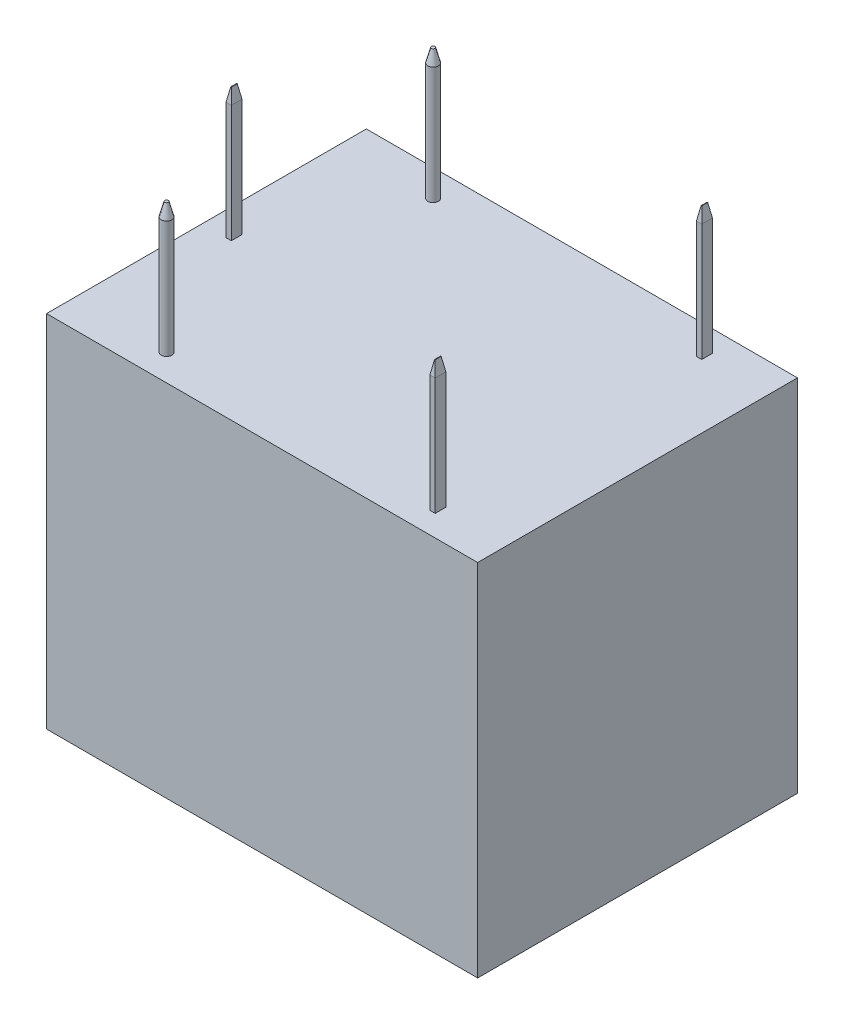
SolidWorks part; units mm, degrees
ref_plane "Front Plane" through (0, 0, 0) normal (0, 0, 1) x (1, 0, 0)
ref_plane "Top Plane" through (0, 0, 0) normal (0, 1, 0) x (1, 0, 0)
ref_plane "Right Plane" through (0, 0, 0) normal (1, 0, 0) x (0, 0, -1)
sketch "Sketch1" plane through (0, 0, 0) normal (0, 1, 0) x (1, 0, 0)
  line L0 (12.5826, 5.166) -> (12.7826, 5.166)
  line L1 (-0.1, 0.2) -> (0.1, 0.2)
  line L2 (-0.1, 0.2) -> (-0.1, -0.2)
  line L3 (-0.1, -0.2) -> (0.1, -0.2)
  line L4 (0.1, 0.2) -> (0.1, -0.2)
  line L5 (12.5826, -4.834) -> (12.7826, -4.834)
  line L6 (12.5826, -4.834) -> (12.5826, -5.234)
  line L7 (12.5826, -5.234) -> (12.7826, -5.234)
  line L8 (12.7826, -4.834) -> (12.7826, -5.234)
  line L11 (12.5826, 5.166) -> (12.5826, 4.766)
  line L12 (12.5826, 4.766) -> (12.7826, 4.766)
  line L13 (12.7826, 5.166) -> (12.7826, 4.766)
  circle A0 centre (2.5049, -5.034) radius 0.2
  circle A1 centre (2.5049, 4.966) radius 0.2
  point P0 (0, 0)
  dimension "D1" = 2
  dimension "D2" = 2
extrude "Boss-Extrude1" add sketch "Sketch1" along normal blind 17.9
sketch "Sketch2" plane through (0, 0, 0) normal (0, 1, 0) x (1, 0, 0)
  line L6 (15.1744, 5.965) -> (-1, 5.965)
  line L7 (15.1744, 5.965) -> (15.1744, -6.0332)
  line L8 (15.1744, -6.0332) -> (-1, -6.0332)
  line L9 (-1, 5.965) -> (-1, -6.0332)
extrude "Boss-Extrude2" add sketch "Sketch2" along normal blind 13.5
sketch "Sketch3" plane through (0, 17.9, 0) normal (0, 1, 0) x (1, 0, 0)
  line L1 (12.5826, -4.834) -> (12.7826, -4.834)
  line L2 (12.5826, -4.834) -> (12.5826, -5.234)
  line L3 (12.5826, -5.234) -> (12.7826, -5.234)
  line L4 (12.7826, -4.834) -> (12.7826, -5.234)
extrude "Boss-Extrude3" add sketch "Sketch3" along normal blind 0.5 draft 10 separate body
sketch "Sketch4" plane through (0, 17.9, 0) normal (0, 1, 0) x (1, 0, 0)
  line L1 (12.5826, 5.166) -> (12.7826, 5.166)
  line L2 (12.5826, 5.166) -> (12.5826, 4.766)
  line L3 (12.5826, 4.766) -> (12.7826, 4.766)
  line L4 (12.7826, 5.166) -> (12.7826, 4.766)
extrude "Boss-Extrude4" add sketch "Sketch4" along normal blind 0.5 draft 10
sketch "Sketch5" plane through (0, 17.9, 0) normal (0, 1, 0) x (1, 0, 0)
  line L0 (0.1, -0.2) -> (0.1, 0.2) construction
  line L1 (-0.1, 0.2) -> (0.1, 0.2)
  line L2 (-0.1, 0.2) -> (-0.1, -0.2)
  line L3 (-0.1, -0.2) -> (0.1, -0.2)
  line L4 (0.1, 0.2) -> (0.1, -0.2)
extrude "Boss-Extrude5" add sketch "Sketch5" along normal blind 0.5 draft 10
sketch "Sketch6" plane through (0, 17.9, 0) normal (0, 1, 0) x (1, 0, 0)
  circle A0 centre (2.5049, 4.966) radius 0.2
extrude "Boss-Extrude6" add sketch "Sketch6" along normal blind 0.5 draft 15
sketch "Sketch7" plane through (0, 17.9, 0) normal (0, 1, 0) x (1, 0, 0)
  circle A0 centre (2.5049, -5.034) radius 0.2
extrude "Boss-Extrude7" add sketch "Sketch7" along normal blind 0.5 draft 15
sketch "Sketch8" plane through (0, 0, 0) normal (0, -1, 0) x (1, 0, 0)
  line L0 (-1, 6.0332) -> (-1, -5.965) construction
  line L1 (-1, -5.965) -> (-1, 0.0341) construction
  line L2 (-1, 0.0341) -> (-1, -0.9632) construction
  line L3 (-1, -0.9632) -> (-1, 1.0389) construction
  line L5 (-1, 1.0389) -> (-0.2442, 1.0389)
  line L6 (-1, 1.0389) -> (-1, -0.9632)
  line L7 (-1, -0.9632) -> (-0.2442, -0.9632)
  line L8 (-0.2442, 1.0389) -> (-0.2442, -0.9632)
extrude "Cut-Extrude1" cut sketch "Sketch8" against normal blind 0.5
sketch "Sketch9" plane through (0, 0, 0) normal (0, -1, 0) x (1, 0, 0)
  line L0 (-1, 2.9129) -> (15.1097, 2.9129) construction
  line L1 (-1, 1.0389) -> (-1, 6.0332) construction
  text T0 "   YLE / ARPE" font "Arial Narrow" height in points 8
extrude "Boss-Extrude8" add sketch "Sketch9" along normal blind 0.01
sketch "Sketch10" plane through (0, 0, 0) normal (0, -1, 0) x (1, 0, 0)
  line L0 (-1, -2.6815) -> (14.9897, -2.6815) construction
  line L1 (-1, -5.965) -> (-1, -0.9632) construction
  text T0 "      YA318-2A-U" font "Arial Narrow" height in points 6
extrude "Boss-Extrude9" add sketch "Sketch10" along normal blind 0.01
sketch "Sketch11" plane through (0, 0, 0) normal (0, -1, 0) x (1, 0, 0)
  line L0 (-1, -5.3851) -> (15.1744, -5.3851) construction
  line L1 (-1, -5.965) -> (-1, -0.9632) construction
  line L2 (15.1744, 6.0332) -> (15.1744, -5.965) construction
  text T0 "      12V  2X10A" font "Arial Narrow" height in points 6
extrude "Boss-Extrude10" add sketch "Sketch11" along normal blind 0.01
